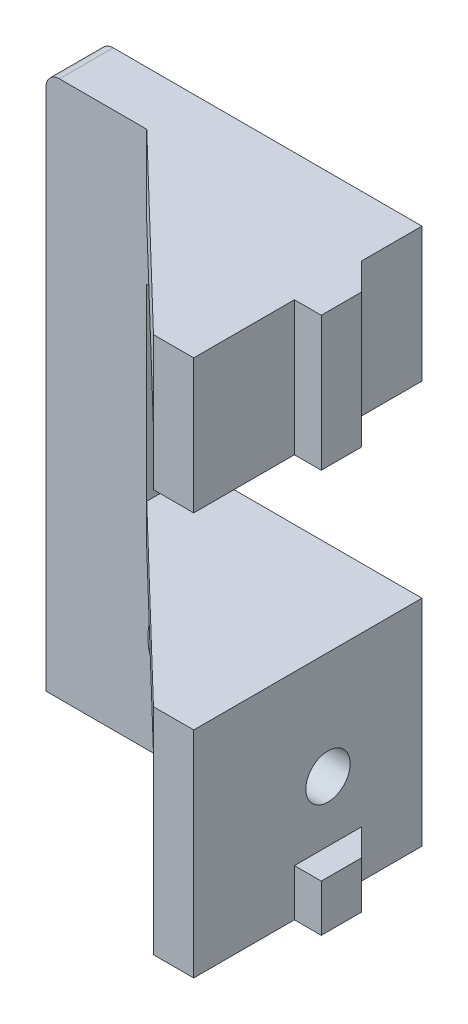
SolidWorks part; units mm, degrees
ref_plane "Front Plane" through (0, 0, 0) normal (0, 0, 1) x (1, 0, 0)
ref_plane "Top Plane" through (0, 0, 0) normal (0, 1, 0) x (1, 0, 0)
ref_plane "Right Plane" through (0, 0, 0) normal (1, 0, 0) x (0, 0, -1)
sketch "Sketch1" plane through (0, 0, 0) normal (0, 0, 1) x (1, 0, 0)
  line L1 (-26.7581, 33.2419) -> (-2.7581, 33.2419)
  line L2 (-26.7581, 33.2419) -> (-26.7581, -6.7581)
  line L3 (-26.7581, -6.7581) -> (-2.7581, -6.7581)
  line L4 (-2.7581, 33.2419) -> (-2.7581, -6.7581)
  dimension "D1" = 40
  dimension "D2" = 24
extrude "Boss-Extrude1" add sketch "Sketch1" along normal blind 4
fillet "Fillet1" radius 1 1 edges at (-26.7581, 33.2419, 2)
sketch "Sketch3" plane through (0, 0, 0) normal (0, 0, -1) x (-1, 0, 0)
  line L0 (2.7581, -6.7581) -> (2.7581, 33.2419) construction
  line L1 (2.7581, 9.2419) -> (19.2581, 9.2419)
  line L2 (2.7581, 9.2419) -> (2.7581, 23.2419)
  line L3 (2.7581, 23.2419) -> (19.2581, 23.2419)
  line L4 (19.2581, 9.2419) -> (19.2581, 23.2419)
  line L5 (26.7581, -6.7581) -> (2.7581, -6.7581) construction
  dimension "D1" = 14
  dimension "D2" = 16.5
  dimension "D3" = 16
extrude "Cut-Extrude2" cut sketch "Sketch3" against normal through all both and the other way through all
sketch "Sketch5" plane through (0, 0, 4) normal (0, 0, 1) x (1, 0, 0)
  line L0 (-26.7581, -6.7581) -> (-2.7581, -6.7581) construction
  line L1 (-2.7581, 9.2419) -> (-5.7581, 9.2419)
  line L2 (-2.7581, 9.2419) -> (-2.7581, -6.7581)
  line L3 (-2.7581, -6.7581) -> (-5.7581, -6.7581)
  line L4 (-5.7581, 9.2419) -> (-5.7581, -6.7581)
  dimension "D1" = 3
extrude "Boss-Extrude2" add sketch "Sketch5" along normal blind 13
sketch "Sketch6" plane through (0, -6.7581, 0) normal (0, -1, 0) x (1, 0, 0)
  line L0 (-5.7581, 17) -> (-16.6664, 4)
  line L1 (-26.7581, 4) -> (-5.7581, 4) construction
  line L2 (-16.6664, 4) -> (-5.7581, 4)
  line L3 (-5.7581, 4) -> (-5.7581, 17)
extrude "Boss-Extrude3" add sketch "Sketch6" against normal blind 3
sketch "Sketch7" plane through (0, 9.2419, 0) normal (0, 1, 0) x (1, 0, 0)
  line L0 (-5.7581, -17) -> (-19.2581, -4)
  line L1 (-19.2581, -4) -> (-5.7581, -4)
  line L2 (-5.7581, -4) -> (-5.7581, -17)
extrude "Boss-Extrude4" add sketch "Sketch7" against normal blind 3
sketch "Sketch8" plane through (-5.7581, 0, 0) normal (-1, 0, 0) x (0, 0, 1)
  line L0 (17, 6.2419) -> (17, -3.7581) construction
  line L1 (17, -6.7581) -> (4, -6.7581) construction
  circle A0 centre (7, 1.2419) radius 1.65
  dimension "D1" = 3.3
  dimension "D2" = 10
  dimension "D3" = 8
extrude "Cut-Extrude4" cut sketch "Sketch8" against normal blind 3
sketch "Sketch9" plane through (0, 0, 4) normal (0, 0, 1) x (1, 0, 0)
  line L0 (-19.2581, 23.2419) -> (-2.7581, 23.2419) construction
  line L1 (-2.7581, 33.2419) -> (-5.7581, 33.2419)
  line L2 (-2.7581, 33.2419) -> (-2.7581, 23.2419)
  line L3 (-2.7581, 23.2419) -> (-5.7581, 23.2419)
  line L4 (-5.7581, 33.2419) -> (-5.7581, 23.2419)
  dimension "D1" = 3
extrude "Boss-Extrude5" add sketch "Sketch9" along normal blind 13
sketch "Sketch10" plane through (0, 33.2419, 0) normal (0, 1, 0) x (1, 0, 0)
  line L0 (-5.7581, -17) -> (-19.2581, -4)
  line L1 (-19.2581, -4) -> (-5.7581, -4)
  line L2 (-5.7581, -4) -> (-5.7581, -17)
extrude "Boss-Extrude6" add sketch "Sketch10" against normal blind 6
sketch "Sketch11" plane through (-2.7581, 0, 0) normal (1, 0, 0) x (0, 0, -1)
  line L0 (-17, 33.2419) -> (0, 33.2419) construction
  line L1 (-9.5, 33.2419) -> (-4.5, 33.2419)
  line L2 (-9.5, 33.2419) -> (-9.5, 23.2419)
  line L3 (-9.5, 23.2419) -> (-4.5, 23.2419)
  line L4 (-4.5, 33.2419) -> (-4.5, 23.2419)
  line L5 (-17, 23.2419) -> (0, 23.2419) construction
  line L6 (-17, 23.2419) -> (-17, 33.2419) construction
  dimension "D1" = 5
  dimension "D2" = 7.5
extrude "Boss-Extrude7" add sketch "Sketch11" along normal blind 2
chamfer "Chamfer1" distance 2 angle 45 1 edges at (-0.7581, 28.2419, 4.5)
sketch "Sketch12" plane through (0, 0, 0) normal (0, 0, -1) x (-1, 0, 0)
  line L0 (26.7581, -6.7581) -> (2.7581, -6.7581) construction
  line L5 (2.7581, -6.7581) -> (2.7581, 9.2419) construction
  circle A0 centre (14.7581, 1.2419) radius 3.1
  dimension "D1" = 6.2
  dimension "D2" = 8
  dimension "D4" = 12
extrude "Cut-Extrude5" cut sketch "Sketch12" against normal blind 3.1
sketch "Sketch17" plane through (0, 0, 4) normal (0, 0, 1) x (1, 0, 0)
  circle A1 centre (-14.7581, 1.2419) radius 4
  dimension "D1" = 8
extrude "Boss-Extrude8" add sketch "Sketch17" along normal blind 1
fillet "Fillet3" radius 1 1 edges at (-10.7581, 1.2419, 5)
sketch "Sketch21" plane through (0, 0, 0) normal (0, 0, -1) x (-1, 0, 0)
  circle A0 centre (14.7581, 1.2419) radius 2.25
  dimension "D1" = 4.5
extrude "Boss-Extrude11" add sketch "Sketch21" against normal blind 2.9 separate body contours A0
sketch "Sketch23" plane through (-2.7581, 0, 0) normal (1, 0, 0) x (0, 0, -1)
  line L0 (-17, -6.7581) -> (0, -6.7581) construction
  line L1 (-9.5, -6.7581) -> (-4.5, -6.7581)
  line L2 (-9.5, -6.7581) -> (-9.5, -3.2581)
  line L3 (-9.5, -3.2581) -> (-4.5, -3.2581)
  line L4 (-4.5, -6.7581) -> (-4.5, -3.2581)
  dimension "D1" = 3.5
extrude "Boss-Extrude12" add sketch "Sketch23" along normal blind 2
chamfer "Chamfer2" distance 2 angle 45 1 edges at (-0.7581, -5.0081, 4.5)
fillet "Fillet6" radius 0.5 1 edges at (-17.8581, 1.2419, 0)
sketch "Sketch24" plane through (0, 0, 0) normal (0, 0, -1) x (-1, 0, 0)
  line L0 (2.7581, 23.2419) -> (19.2581, 23.2419) construction
  line L1 (2.7581, 23.2419) -> (2.7581, 33.2419) construction
  circle A0 centre (10.5081, 25.7419) radius 1.25
  dimension "D1" = 2.5
  dimension "D2" = 2.5
  dimension "D3" = 7.75
extrude "Cut-Extrude6" cut sketch "Sketch24" against normal blind 2.5 contours A0
fillet "Fillet7" radius 0.5 1 edges at (-11.7581, 25.7419, 0)
